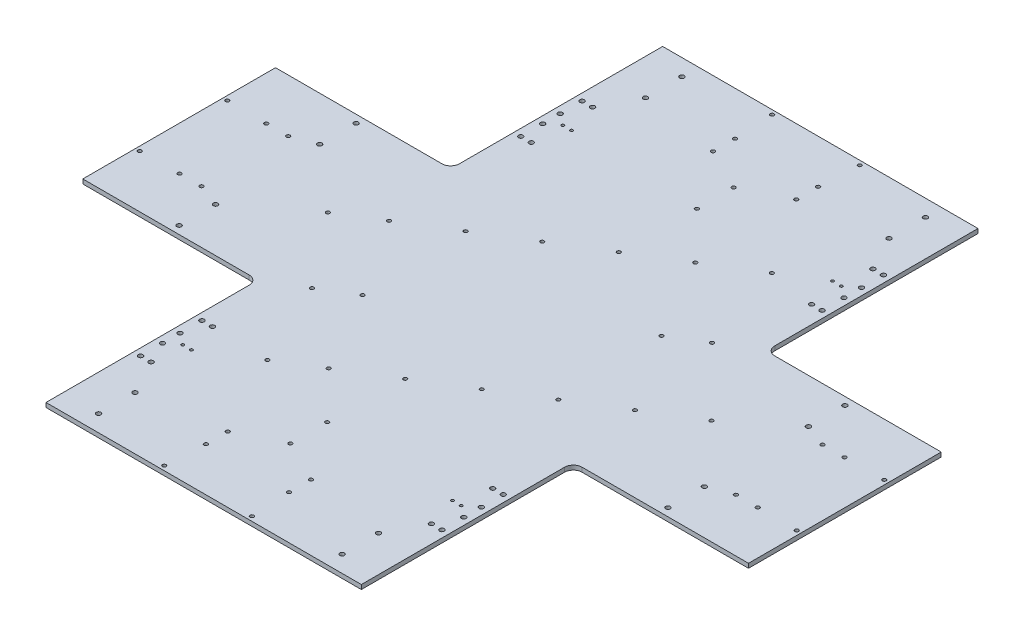
SolidWorks part; units mm, degrees
material "3.0205 (EN-AW 1200)"
ref_plane "前视基准面" through (0, 0, 0) normal (0, 0, 1) x (1, 0, 0)
ref_plane "上视基准面" through (0, 0, 0) normal (0, 1, 0) x (1, 0, 0)
ref_plane "右视基准面" through (0, 0, 0) normal (1, 0, 0) x (0, 0, -1)
other "Configuration Table"
sketch "Sketch1" plane through (0, 0, 0) normal (0, 1, 0) x (1, 0, 0)
  line L0 (180, 352) -> (-180, 352)
  line L1 (-180, 352) -> (-180, 110)
  line L2 (-180, 110) -> (-380, 110)
  line L5 (-380, 110) -> (-380, -110)
  line L6 (0, 352) -> (0, -66.8675) construction
  line L7 (-380, 0) -> (131.0517, 0) construction
  line L8 (380, 110) -> (380, -110)
  line L11 (180, 110) -> (380, 110)
  line L12 (180, 352) -> (180, 110)
  line L13 (180, -352) -> (180, -110)
  line L14 (180, -110) -> (380, -110)
  line L19 (-180, -110) -> (-380, -110)
  line L20 (-180, -352) -> (-180, -110)
  line L21 (180, -352) -> (-180, -352)
  point P21 (380, 0)
  dimension "D1" = 180
  dimension "D2" = 200
  dimension "D3" = 110
  dimension "D4" = 242
extrude "Boss-Extrude1" add sketch "Sketch1" along normal blind 5
sketch "Sketch2" plane through (0, 5, 0) normal (0, 1, 0) x (1, 0, 0)
  line L2 (380, 110) -> (180, 110) construction
  line L3 (380, -110) -> (380, 110) construction
  line L4 (-56.7455, 0) -> (47.5165, 0) construction
  line L5 (0, 54.7142) -> (0, -64.2255) construction
  line L7 (180, 352) -> (-180, 352) construction
  circle A0 centre (330, 49.5) radius 2.125
  circle A1 centre (305, 49.5) radius 2.125
  circle A7 centre (305, -49.5) radius 2.125
  circle A8 centre (330, -49.5) radius 2.125
  circle A9 centre (-330, -49.5) radius 2.125
  circle A10 centre (-305, -49.5) radius 2.125
  circle A13 centre (-305, 49.5) radius 2.125
  circle A14 centre (-330, 49.5) radius 2.125
  circle A15 centre (47.5, 302) radius 2.125
  circle A16 centre (47.5, 277) radius 2.125
  circle A17 centre (-47.5, 277) radius 2.125
  circle A18 centre (-47.5, 302) radius 2.125
  circle A19 centre (-47.5, -302) radius 2.125
  circle A20 centre (-47.5, -277) radius 2.125
  circle A21 centre (47.5, -277) radius 2.125
  circle A22 centre (47.5, -302) radius 2.125
  dimension "D1" = 60.5
  dimension "D5" = 4.25
  dimension "D7" = 4.25
  dimension "D9" = 4.25
  dimension "D10" = 4.25
  dimension "D4" = 25
  dimension "D6" = 50
  dimension "D11" = 47.5
  dimension "D12" = 50
  dimension "D13" = 25
extrude "Cut-Extrude1" cut sketch "Sketch2" against normal blind 3
sketch "Sketch4" plane through (0, 5, 0) normal (0, 1, 0) x (1, 0, 0)
  line L0 (-180, 352) -> (-180, 110) construction
  line L1 (180, 352) -> (-180, 352) construction
  line L2 (0, 46.9886) -> (0, -40.2904) construction
  line L3 (-35.103, 0) -> (92.4951, 0) construction
  line L5 (180, -352) -> (180, -110) construction
  circle A0 centre (-172, 182) radius 2.6
  circle A1 centre (-160, 182) radius 2.6
  circle A2 centre (-172, 207) radius 2.6
  circle A3 centre (-172, 227) radius 2.6
  circle A4 centre (-172, 252) radius 2.6
  circle A5 centre (-160, 252) radius 2.6
  circle A6 centre (160, 252) radius 2.6
  circle A7 centre (172, 252) radius 2.6
  circle A8 centre (172, 227) radius 2.6
  circle A9 centre (172, 207) radius 2.6
  circle A10 centre (160, 182) radius 2.6
  circle A11 centre (172, 182) radius 2.6
  circle A12 centre (172, -182) radius 2.6
  circle A13 centre (160, -182) radius 2.6
  circle A14 centre (172, -207) radius 2.6
  circle A15 centre (172, -227) radius 2.6
  circle A16 centre (172, -252) radius 2.6
  circle A17 centre (160, -252) radius 2.6
  circle A18 centre (-160, -252) radius 2.6
  circle A19 centre (-172, -252) radius 2.6
  circle A20 centre (-172, -227) radius 2.6
  circle A21 centre (-172, -207) radius 2.6
  circle A22 centre (-160, -182) radius 2.6
  circle A23 centre (-172, -182) radius 2.6
  circle A24 centre (159, -217) radius 1.6
  circle A25 centre (-159, -217) radius 1.6
  circle A26 centre (159, 217) radius 1.6
  circle A27 centre (-159, 217) radius 1.6
  circle A28 centre (149, -217) radius 1.6
  circle A29 centre (-149, -217) radius 1.6
  circle A30 centre (149, 217) radius 1.6
  circle A31 centre (-149, 217) radius 1.6
  dimension "D3" = 5.2
  dimension "D4" = 5.2
  dimension "D5" = 8
  dimension "D6" = 8
  dimension "D9" = 5.2
  dimension "D10" = 5.2
  dimension "D11" = 5.2
  dimension "D12" = 5.2
  dimension "D19" = 3.2
  dimension "D20" = 21
  dimension "D21" = 10
  dimension "D22" = 3.2
  dimension "D23" = 10
  dimension "D1" = 8
  dimension "D2" = 20
  dimension "D7" = 8
  dimension "D8" = 20
  dimension "D13" = 25
  dimension "D14" = 20
  dimension "D15" = 25
  dimension "D16" = 25
  dimension "D17" = 100
  dimension "D18" = 0
extrude "Cut-Extrude3" cut sketch "Sketch4" against normal blind 10
sketch "Sketch5" plane through (0, 5, 0) normal (0, 1, 0) x (1, 0, 0)
  line L0 (180, 352) -> (-180, 352) construction
  line L5 (-46.9195, 0) -> (66.6223, 0) construction
  line L6 (0, 59.0569) -> (0, -54.4849) construction
  line L10 (-380, 110) -> (-380, -110) construction
  line L12 (-180, 110) -> (-380, 110) construction
  line L13 (-380, -110) -> (-180, -110) construction
  circle A0 centre (-50, 347) radius 2.1
  circle A1 centre (50, 347) radius 2.1
  circle A2 centre (50, -347) radius 2.1
  circle A3 centre (-50, -347) radius 2.1
  circle A4 centre (-375, 50) radius 2.1
  circle A5 centre (-375, -50) radius 2.1
  circle A6 centre (375, -50) radius 2.1
  circle A7 centre (375, 50) radius 2.1
  dimension "D1" = 4.2
  dimension "D2" = 4.2
  dimension "D3" = 60
  dimension "D6" = 4.2
  dimension "D7" = 4.2
  dimension "5" = 5
  dimension "D4" = 50
  dimension "D5" = 50
  dimension "D8" = 60
  dimension "D9" = 5
  dimension "D10" = 5
extrude "Cut-Extrude4" cut sketch "Sketch5" against normal blind 10
fillet "Fillet1" radius 10 4 edges at (-180, 2.5, -110) (-180, 2.5, 110) (180, 2.5, 110) (180, 2.5, -110)
sketch "Sketch6" plane through (0, 5, 0) normal (0, 1, 0) x (1, 0, 0)
  line L0 (180, 352) -> (-180, 352) construction
  line L2 (180, 120) -> (180, 352) construction
  line L3 (-64.416, 0) -> (103.2752, 0) construction
  line L4 (0, 86.0771) -> (0, -73.7041) construction
  line L5 (380, 110) -> (190, 110) construction
  line L6 (380, -110) -> (380, 110) construction
  circle A0 centre (139, 333) radius 2.6
  circle A1 centre (139, 291.4) radius 2.6
  circle A2 centre (139, -291.4) radius 2.6
  circle A3 centre (139, -333) radius 2.6
  circle A4 centre (-139, -333) radius 2.6
  circle A5 centre (-139, -291.4) radius 2.6
  circle A6 centre (-139, 291.4) radius 2.6
  circle A7 centre (-139, 333) radius 2.6
  circle A8 centre (279, 101) radius 2.6
  circle A9 centre (279, 59.4) radius 2.6
  circle A10 centre (279, -59.4) radius 2.6
  circle A11 centre (279, -101) radius 2.6
  circle A12 centre (-279, -101) radius 2.6
  circle A13 centre (-279, -59.4) radius 2.6
  circle A14 centre (-279, 59.4) radius 2.6
  circle A15 centre (-279, 101) radius 2.6
  dimension "D1" = 5.2
  dimension "D2" = 5.2
  dimension "D6" = 5.2
  dimension "D7" = 5.2
  dimension "D3" = 19
  dimension "D4" = 41
  dimension "D5" = 41.6
  dimension "D8" = 9
  dimension "D9" = 41.6
  dimension "D10" = 101
extrude "Cut-Extrude5" cut sketch "Sketch6" against normal blind 10
sketch "Sketch7" plane through (0, 5, 0) normal (0, 1, 0) x (1, 0, 0)
  line L0 (197.463, 121.9013) -> (-168.3949, -103.9565) construction
  line L1 (180, 235.6925) -> (-379.973, -110) construction
  line L2 (144.6063, 226.5583) -> (333.7962, -79.9026) construction
  line L3 (-55.682, 90.1971) -> (55.682, -90.1971) construction
  line L4 (-182.9289, -112.9289) -> (182.9289, 112.9289) construction
  circle A0 centre (-55.682, 90.1971) radius 2.1
  circle A1 centre (-1.6489, 123.5538) radius 2.1
  circle A2 centre (52.3842, 156.9105) radius 2.1
  circle A3 centre (106.4174, 190.2672) radius 2.1
  circle A4 centre (-109.7152, 56.8404) radius 2.1
  circle A5 centre (-163.7483, 23.4837) radius 2.1
  circle A6 centre (-206.9749, -3.2017) radius 2.1
  circle A7 centre (-95.6108, -183.5958) radius 2.1
  circle A8 centre (-52.3842, -156.9105) radius 2.1
  circle A9 centre (1.6489, -123.5538) radius 2.1
  circle A10 centre (217.7815, 9.873) radius 2.1
  circle A11 centre (163.7483, -23.4837) radius 2.1
  circle A12 centre (109.7152, -56.8404) radius 2.1
  circle A13 centre (55.682, -90.1971) radius 2.1
  arc A14 (180, 120) -> (190, 110) centre (190, 120) ccw construction
  arc A15 (-180, -120) -> (-190, -110) centre (-190, -120) ccw construction
  point P35 (0, 0)
  point P36 (182.9289, 112.9289)
  point P37 (-182.9289, -112.9289)
  dimension "D1" = 4.2
  dimension "D2" = 4.2
  dimension "D3" = 4.2
  dimension "D4" = 4.2
  dimension "D5" = 4.2
  dimension "D6" = 4.2
  dimension "D7" = 4.2
  dimension "D8" = 63.5
  dimension "D9" = 63.5
  dimension "D10" = 50.8
  dimension "D11" = 63.5
  dimension "D12" = 63.5
  dimension "D13" = 63.5
  dimension "D14" = 0
  dimension "D15" = 0
  dimension "D16" = 106
extrude "Cut-Extrude6" cut sketch "Sketch7" against normal blind 10
sketch "Sketch8" plane through (0, 5, 0) normal (0, 1, 0) x (1, 0, 0)
  line L0 (182.9289, 112.9289) -> (-182.9289, -112.9289) construction
  line L1 (93.4791, 124.5685) -> (153.9966, 26.5386) construction
  line L2 (-144.8767, -41.3115) -> (-92.88, -125.5389) construction
  line L3 (0, 77.1364) -> (0, -65.7088) construction
  line L4 (-60.3124, 0) -> (69.2005, 0) construction
  line L5 (180, 352) -> (-180, 352) construction
  arc A0 (180, 120) -> (190, 110) centre (190, 120) ccw construction
  arc A1 (-180, -120) -> (-190, -110) centre (-190, -120) ccw construction
  circle A2 centre (-141.2341, -87.1891) radius 2.1
  circle A3 centre (-105.4956, -65.1264) radius 2.1
  circle A4 centre (105.4956, 65.1264) radius 2.1
  circle A5 centre (141.2341, 87.1891) radius 2.1
  circle A6 centre (0, 253) radius 2.1
  circle A7 centre (0, 211) radius 2.1
  circle A8 centre (0, -211) radius 2.1
  circle A9 centre (0, -253) radius 2.1
  dimension "D3" = 4.2
  dimension "D4" = 4.2
  dimension "D5" = 4.2
  dimension "D6" = 4.2
  dimension "D8" = 21
  dimension "D11" = 4.2
  dimension "D12" = 4.2
  dimension "D1" = 70
  dimension "D2" = 70
  dimension "D7" = 21
  dimension "D9" = 21
  dimension "D10" = 21
  dimension "D13" = 99
  dimension "D14" = 42
extrude "Cut-Extrude7" cut sketch "Sketch8" against normal blind 10
